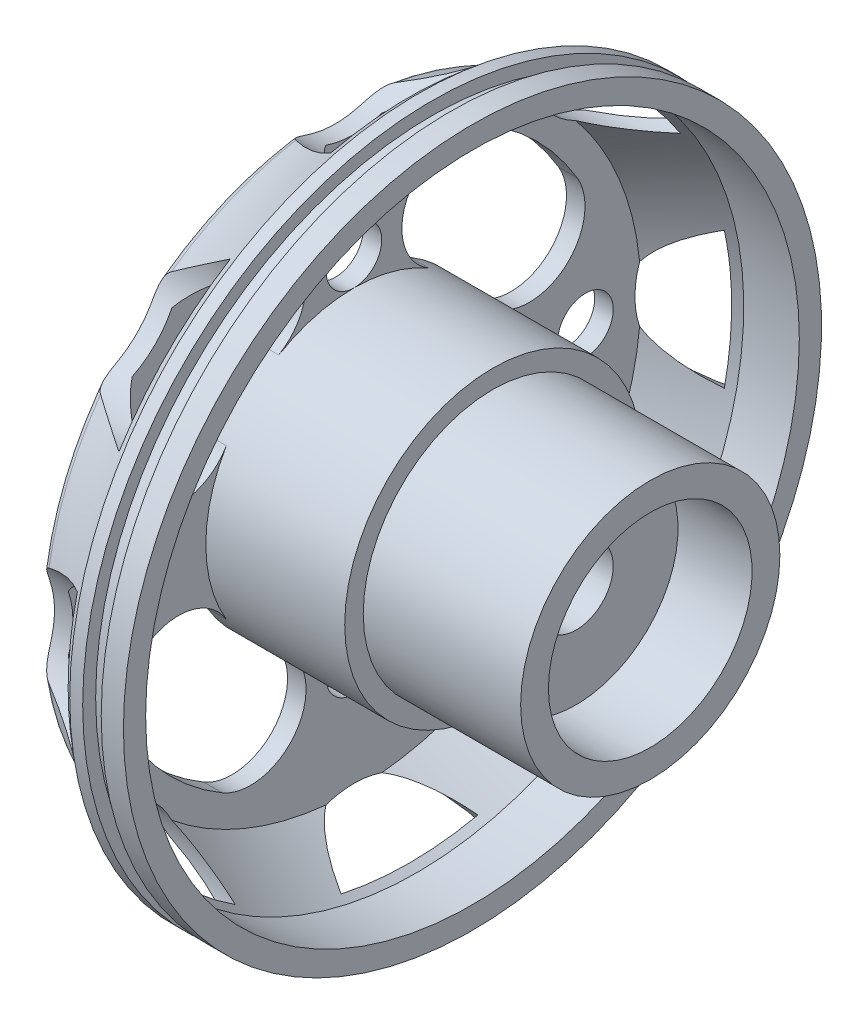
SolidWorks part; units mm, degrees
ref_plane "Front Plane" through (0, 0, 0) normal (0, 0, 1) x (1, 0, 0)
ref_plane "Top Plane" through (0, 0, 0) normal (0, 1, 0) x (1, 0, 0)
ref_plane "Right Plane" through (0, 0, 0) normal (1, 0, 0) x (0, 0, -1)
sketch "Sketch1" plane through (0, 0, 0) normal (0, 0, 1) x (1, 0, 0)
  line L0 (0, 18.0576) -> (0, 0) construction
  line L1 (0, 0) -> (33.6629, 0) construction
  line L2 (17, 5.5) -> (13, 5.5)
  line L3 (13, 5.5) -> (13, 2)
  line L4 (13, 2) -> (4, 2)
  line L5 (4, 2) -> (4, 5.5)
  line L6 (4, 5.5) -> (0, 5.5)
  line L7 (0, 5.5) -> (0, 16)
  line L8 (4.5, 18.85) -> (5.2, 18.85)
  line L9 (7.4, 18.85) -> (7.4, 17.65)
  line L10 (7.4, 17.65) -> (4.4, 17.65)
  line L11 (4.4, 17.65) -> (1, 15.5)
  line L12 (1, 15.5) -> (1, 8)
  line L13 (1, 8) -> (8.5, 8)
  line L14 (8.5, 8) -> (8.5, 7)
  line L15 (8.5, 7) -> (17, 7)
  line L16 (17, 7) -> (17, 5.5)
  line L17 (6.2, 18.85) -> (7.4, 18.85)
  line L19 (5.2, 18.85) -> (5.2, 18.15)
  line L20 (5.2, 18.15) -> (6.2, 18.15)
  line L21 (6.2, 18.85) -> (6.2, 18.15)
  arc A1 (0, 16) -> (4.5, 18.85) centre (-7.4048, 32.6693) ccw
  dimension "D19" = 18.24
  dimension "D1" = 18.85
  dimension "D2" = 17
  dimension "D3" = 2
  dimension "D4" = 4
  dimension "D5" = 1
  dimension "D6" = 7
  dimension "D7" = 8
  dimension "D8" = 4.5
  dimension "D9" = 5.5
  dimension "D10" = 2.9
  dimension "D11" = 3
  dimension "D12" = 4.5
  dimension "D13" = 1.2
  dimension "D14" = 16
  dimension "D15" = 7.5
  dimension "D16" = 0.7
  dimension "D17" = 1
  dimension "D18" = 0.7
revolve "Revolve1" add sketch "Sketch1" angle 360 about L1
fillet "Fillet1" radius 1 1 edges at (0, 0, 16)
sketch "Sketch2" plane through (0, 0, 0) normal (-1, 0, 0) x (0, 0, 1)
  line L0 (21.2806, 0) -> (0, 0) construction
  line L1 (0, 0) -> (0, 19.6679) construction
  line L2 (0, 0) -> (17.9851, 17.9851) construction
  arc A0 (9.4757, 5.5866) -> (5.5866, 9.4757) centre (0, 0) ccw construction
  arc A1 (12.06, 7.1103) -> (7.1103, 12.06) centre (0, 0) ccw
  arc A2 (6.8914, 4.063) -> (4.063, 6.8914) centre (0, 0) ccw
  arc A3 (6.8914, 4.063) -> (12.06, 7.1103) centre (9.4757, 5.5866) ccw
  arc A4 (7.1103, 12.06) -> (4.063, 6.8914) centre (5.5866, 9.4757) ccw
  arc A5 (4.063, -6.8914) -> (6.8914, -4.063) centre (0, 0) ccw
  arc A6 (4.063, -6.8914) -> (7.1103, -12.06) centre (5.5866, -9.4757) ccw
  arc A7 (12.06, -7.1103) -> (6.8914, -4.063) centre (9.4757, -5.5866) ccw
  arc A8 (7.1103, -12.06) -> (12.06, -7.1103) centre (0, 0) ccw
  arc A9 (5.5866, -9.4757) -> (9.4757, -5.5866) centre (0, 0) ccw construction
  arc A10 (-6.8914, -4.063) -> (-4.063, -6.8914) centre (0, 0) ccw
  arc A11 (-6.8914, -4.063) -> (-12.06, -7.1103) centre (-9.4757, -5.5866) ccw
  arc A12 (-7.1103, -12.06) -> (-4.063, -6.8914) centre (-5.5866, -9.4757) ccw
  arc A13 (-12.06, -7.1103) -> (-7.1103, -12.06) centre (0, 0) ccw
  arc A14 (-9.4757, -5.5866) -> (-5.5866, -9.4757) centre (0, 0) ccw construction
  arc A15 (-4.063, 6.8914) -> (-6.8914, 4.063) centre (0, 0) ccw
  arc A16 (-4.063, 6.8914) -> (-7.1103, 12.06) centre (-5.5866, 9.4757) ccw
  arc A17 (-12.06, 7.1103) -> (-6.8914, 4.063) centre (-9.4757, 5.5866) ccw
  arc A18 (-7.1103, 12.06) -> (-12.06, 7.1103) centre (0, 0) ccw
  arc A19 (-5.5866, 9.4757) -> (-9.4757, 5.5866) centre (0, 0) ccw construction
  arc A20 (9.8445, 16.0751) -> (16.0751, 9.8445) centre (14.0188, 14.0188) ccw
  circle A21 centre (0, 0) radius 18.85 construction
  arc A22 (18.3279, 4.4057) -> (18.3279, -4.4057) centre (19.8256, 0) ccw
  arc A23 (16.0751, -9.8445) -> (9.8445, -16.0751) centre (14.0188, -14.0188) ccw
  arc A24 (4.4057, -18.3279) -> (-4.4057, -18.3279) centre (0, -19.8256) ccw
  arc A25 (-9.8445, -16.0751) -> (-16.0751, -9.8445) centre (-14.0188, -14.0188) ccw
  arc A26 (-18.3279, -4.4057) -> (-18.3279, 4.4057) centre (-19.8256, 0) ccw
  arc A27 (-16.0751, 9.8445) -> (-9.8445, 16.0751) centre (-14.0188, 14.0188) ccw
  arc A28 (-4.4057, 18.3279) -> (4.4057, 18.3279) centre (0, 19.8256) ccw
  arc A29 (4.4057, 18.3279) -> (-4.4057, 18.3279) centre (0, 0) ccw
  arc A30 (-9.8445, 16.0751) -> (-16.0751, 9.8445) centre (0, 0) ccw
  arc A31 (16.0751, 9.8445) -> (9.8445, 16.0751) centre (0, 0) ccw
  arc A32 (18.3279, -4.4057) -> (18.3279, 4.4057) centre (0, 0) ccw
  arc A33 (9.8445, -16.0751) -> (16.0751, -9.8445) centre (0, 0) ccw
  arc A34 (-4.4057, -18.3279) -> (4.4057, -18.3279) centre (0, 0) ccw
  arc A35 (-16.0751, -9.8445) -> (-9.8445, -16.0751) centre (0, 0) ccw
  arc A36 (-18.3279, 4.4057) -> (-18.3279, -4.4057) centre (0, 0) ccw
  point P7 (7.7782, 7.7782)
  point P17 (7.7782, -7.7782)
  point P24 (-7.7782, -7.7782)
  point P31 (-7.7782, 7.7782)
  dimension "D3" = 14
  dimension "D4" = 8
  dimension "D1" = 45
  dimension "D2" = 5.5
  dimension "D5" = 4
  dimension "D6" = 8
extrude "Cut-Extrude3" cut sketch "Sketch2" against normal blind 4
sketch "Sketch3" plane through (0, 0, 0) normal (-1, 0, 0) x (0, 0, 1)
  circle A0 centre (0, 0) radius 9.5 construction
  circle A1 centre (0, 0) radius 12.5 construction
  circle A2 centre (12.5, 0) radius 1.5
  circle A3 centre (-12.5, 0) radius 1.5
  circle A4 centre (0, -9.5) radius 1.5
  circle A5 centre (0, 9.5) radius 1.5
  dimension "D1" = 25
  dimension "D2" = 19
  dimension "D3" = 3
extrude "Cut-Extrude4" cut sketch "Sketch3" against normal blind 4
